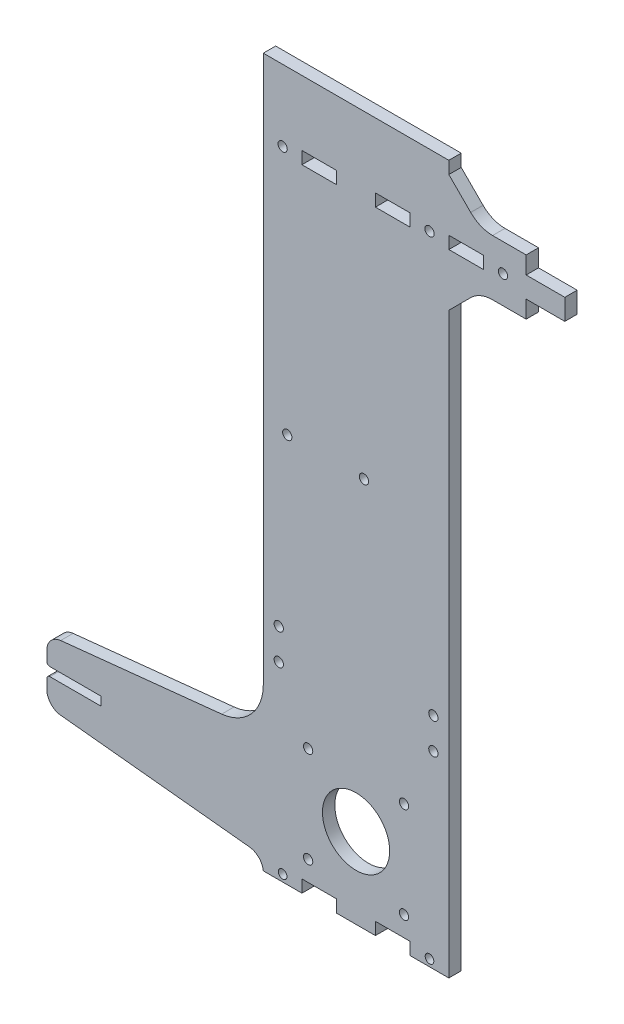
SolidWorks part; units mm, degrees
ref_plane "Спереди" through (0, 0, 0) normal (0, 0, 1) x (1, 0, 0)
ref_plane "Сверху" through (0, 0, 0) normal (0, 1, 0) x (1, 0, 0)
ref_plane "Справа" through (0, 0, 0) normal (1, 0, 0) x (0, 0, -1)
sketch "Эскиз1" plane through (0, 0, 0) normal (0, 0, 1) x (1, 0, 0)
  line L0 (35.6598, -54.71) -> (-35.6598, -54.71) construction
  line L1 (-30, -22) -> (30, -22)
  line L2 (-30, -22) -> (-30, 203)
  line L3 (-30, 203) -> (30, 203)
  line L4 (30, -22) -> (30, 203)
  line L10 (-100, 5.29) -> (-30, 5.29)
  line L11 (-100, 5.29) -> (-100, -14.71)
  line L12 (-100, -14.71) -> (-30, -14.71)
  line L13 (-30, 5.29) -> (-30, -14.71)
  line L14 (-100, 5.29) -> (-30, 12.58)
  line L15 (-100, -14.71) -> (-30, -22)
  line L17 (-100, -3.31) -> (-82.5, -3.31)
  line L18 (-100, -3.31) -> (-100, -6.11)
  line L19 (-100, -6.11) -> (-82.5, -6.11)
  line L20 (-82.5, -3.31) -> (-82.5, -6.11)
  line L24 (30, 183.375) -> (67.5, 183.375)
  line L25 (30, 183.375) -> (30, 176.625)
  line L26 (30, 176.625) -> (67.5, 176.625)
  line L27 (67.5, 183.375) -> (67.5, 176.625)
  line L28 (30, 189) -> (55, 189)
  line L29 (30, 189) -> (30, 171)
  line L30 (30, 171) -> (55, 171)
  line L31 (55, 189) -> (55, 171)
  circle A0 centre (0, 0) radius 10.875
  circle A1 centre (-15.5, 15.5) radius 1.5
  circle A2 centre (15.5, 15.5) radius 1.5
  circle A3 centre (15.5, -15.5) radius 1.5
  circle A4 centre (-15.5, -15.5) radius 1.5
  circle A5 centre (-22.25, 100) radius 1.5
  circle A6 centre (2.55, 100) radius 1.5
  point P14 (0, 0)
  point P16 (0, -22)
  point P28 (-82.5, -4.71)
  point P29 (-100, -4.71)
  point P38 (55, 180)
  point P39 (67.5, 180)
  dimension "D1" = 21.75
  dimension "D4" = 3
  dimension "D14" = 6.75
  dimension "D19" = 3
  dimension "D2" = 15.5
  dimension "D3" = 15.5
  dimension "D6" = 225
  dimension "D7" = 60
  dimension "D8" = 22
  dimension "D9" = 100
  dimension "D10" = 40
  dimension "D11" = 20
  dimension "D12" = 2.8
  dimension "D13" = 17.5
  dimension "D15" = 18
  dimension "D16" = 12.5
  dimension "D17" = 25
  dimension "D18" = 23
  dimension "D20" = 24.8
  dimension "D21" = 7.75
  dimension "D22" = 100
  dimension "D5" = 4
extrude "Бобышка-Вытянуть1" add sketch "Эскиз1" along normal blind 4
fillet "Скругление3" radius 15 1 edges at (-30, 12.58, 2)
fillet "Скругление4" radius 5 2 edges at (-100, -14.71, 2) (-100, 5.29, 2)
fillet "Скругление5" radius 1 2 edges at (-100, -6.11, 2) (-100, -3.31, 2)
sketch "Эскиз2" plane through (0, 0, 4) normal (0, 0, 1) x (1, 0, 0)
  line L0 (-30, -22) -> (30, -22) construction
  line L1 (-30, -22) -> (-17.5, -22)
  line L2 (-30, -22) -> (-30, -26)
  line L3 (-30, -26) -> (-17.5, -26)
  line L4 (-17.5, -22) -> (-17.5, -26)
  line L5 (-6.25, -22) -> (6.25, -22)
  line L6 (-6.25, -22) -> (-6.25, -26)
  line L7 (-6.25, -26) -> (6.25, -26)
  line L8 (6.25, -22) -> (6.25, -26)
  line L10 (30, -22) -> (17.5, -22)
  line L11 (30, -22) -> (30, -26)
  line L12 (30, -26) -> (17.5, -26)
  line L13 (17.5, -22) -> (17.5, -26)
  circle A0 centre (-23.75, -23.75) radius 1.4
  circle A2 centre (23.75, -23.75) radius 1.4
  point P16 (0, -26)
  point P24 (23.75, -26)
  point P26 (-23.75, -26)
  dimension "D3" = 2.8
  dimension "D1" = 4
  dimension "D2" = 12.5
  dimension "D4" = 2.25
extrude "Бобышка-Вытянуть2" add sketch "Эскиз2" against normal through all
fillet "Скругление6" radius 5 1 edges at (-30, -22, 2)
sketch "Эскиз4" plane through (0, 0, 4) normal (0, 0, 1) x (1, 0, 0)
  line L0 (-30, 182) -> (30, 182) construction
  line L1 (-30, 26.099) -> (-30, 203) construction
  line L2 (30, -26) -> (30, 171) construction
  line L3 (-30, 203) -> (30, 203) construction
  line L5 (41.25, 182) -> (53.75, 182)
  line L6 (-30, 182) -> (-17.5, 182)
  line L7 (-30, 182) -> (-30, 178)
  line L8 (-30, 178) -> (-17.5, 178)
  line L9 (-17.5, 182) -> (-17.5, 178)
  line L10 (-6.25, 182) -> (6.25, 182)
  line L11 (-6.25, 182) -> (-6.25, 178)
  line L12 (-6.25, 178) -> (6.25, 178)
  line L13 (6.25, 182) -> (6.25, 178)
  line L14 (30, 182) -> (17.5, 182)
  line L15 (30, 182) -> (30, 178)
  line L16 (30, 178) -> (17.5, 178)
  line L17 (17.5, 182) -> (17.5, 178)
  line L18 (-17.5, 178) -> (-6.25, 178)
  line L19 (-17.5, 178) -> (-17.5, 182)
  line L20 (-17.5, 182) -> (-6.25, 182)
  line L21 (-6.25, 178) -> (-6.25, 182)
  line L22 (6.25, 178) -> (17.5, 178)
  line L23 (6.25, 178) -> (6.25, 182)
  line L24 (6.25, 182) -> (17.5, 182)
  line L25 (17.5, 178) -> (17.5, 182)
  line L26 (41.25, 182) -> (41.25, 178)
  line L27 (41.25, 178) -> (53.75, 178)
  line L28 (53.75, 182) -> (53.75, 178)
  line L29 (30, 178) -> (41.25, 178)
  line L30 (30, 178) -> (30, 182)
  line L31 (30, 182) -> (41.25, 182)
  line L32 (41.25, 178) -> (41.25, 182)
  circle A0 centre (-23.75, 180) radius 1.5
  circle A1 centre (23.75, 180) radius 1.5
  circle A2 centre (47.5, 180) radius 1.5
  point P19 (0, 182)
  point P24 (-17.5, 180)
  point P26 (-23.75, 182)
  point P27 (23.75, 182)
  point P33 (47.5, 182)
  dimension "D4" = 3
  dimension "D1" = 21
  dimension "D2" = 4
  dimension "D3" = 12.5
  dimension "D5" = 11.25
extrude "Вырез-Вытянуть2" cut sketch "Эскиз4" against normal through all contours A1 | A0 | L20 L9 L18 L11 | L24 L13 L22 L17 | L31 L15 L29 L26 | A2
chamfer "Фаска1" distance 10 angle 45 2 edges at (30, 171, 2) (30, 189, 2)
fillet "Скругление7" radius 10 2 edges at (40, 171, 2) (40, 189, 2)
sketch "Эскиз3" plane through (0, 0, 4) normal (0, 0, 1) x (1, 0, 0)
  line L0 (-25, 45) -> (-25, 35) construction
  line L1 (-25, 35) -> (25, 35) construction
  line L2 (25, 35) -> (25, 45) construction
  line L3 (25, 45) -> (-25, 45) construction
  circle A0 centre (-25, 45) radius 1.5
  circle A1 centre (25, 45) radius 1.5
  circle A2 centre (-25, 35) radius 1.5
  circle A3 centre (25, 35) radius 1.5
  point P8 (0, 35)
  dimension "D1" = 3
  dimension "D2" = 10
  dimension "D3" = 50
  dimension "D4" = 35
extrude "Вырез-Вытянуть1" cut sketch "Эскиз3" against normal through all contours A0 | A1 | A3 | A2
sketch "Эскиз5" [suppressed] plane through (0, 0, 4) normal (0, 0, 1) x (1, 0, 0)
  line L0 (17.5, 154.25) -> (17.5, 145.75) construction
  line L1 (-16.75, 144.125) -> (1.75, 144.125)
  line L2 (-16.75, 144.125) -> (-16.75, 155.875)
  line L3 (-16.75, 155.875) -> (1.75, 155.875)
  line L4 (1.75, 144.125) -> (1.75, 155.875)
  line L5 (-16.75, 144.125) -> (1.75, 155.875) construction
  line L6 (-16.75, 155.875) -> (1.75, 144.125) construction
  circle A0 centre (17.5, 154.25) radius 2.375
  circle A1 centre (17.5, 145.75) radius 2.375
  point P0 (-7.5, 150)
  point P9 (17.5, 150)
  dimension "D3" = 4.75
  dimension "D1" = 18.5
  dimension "D2" = 11.75
  dimension "D4" = 8.5
  dimension "D5" = 150
  dimension "D6" = 25
  dimension "D7" = 7.5
extrude "Вырез-Вытянуть3" [suppressed] cut sketch "Эскиз5" against normal through all
